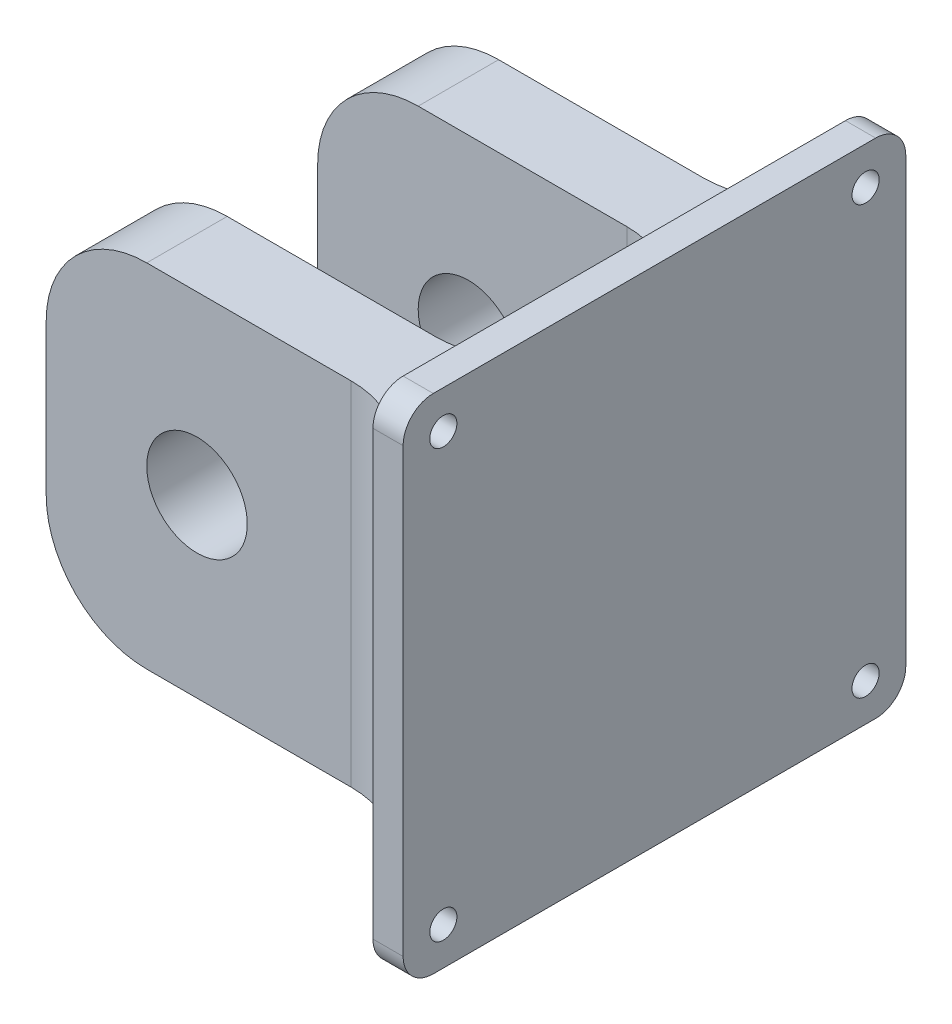
SolidWorks part; units mm, degrees
ref_plane "Plan de face" through (0, 0, 0) normal (0, 0, 1) x (1, 0, 0)
ref_plane "Plan de dessus" through (0, 0, 0) normal (0, 1, 0) x (1, 0, 0)
ref_plane "Plan de droite" through (0, 0, 0) normal (1, 0, 0) x (0, 0, -1)
sketch "Esquisse3" plane through (0, 0, 0) normal (1, 0, 0) x (0, 0, -1)
  line L1 (-25, -25) -> (25, -25)
  line L2 (-25, -25) -> (-25, 25)
  line L3 (-25, 25) -> (25, 25)
  line L4 (25, -25) -> (25, 25)
  line L5 (-25, -25) -> (25, 25) construction
  line L6 (-25, 25) -> (25, -25) construction
  point P0 (0, 0)
  dimension "D1" = 50
  dimension "D2" = 50
sketch "Esquisse4" plane through (0, 0, 0) normal (1, 0, 0) x (0, 0, -1)
  line L1 (-17.5, -17.5) -> (17.5, -17.5)
  line L2 (-17.5, -17.5) -> (-17.5, 17.5)
  line L3 (-17.5, 17.5) -> (17.5, 17.5)
  line L4 (17.5, -17.5) -> (17.5, 17.5)
  line L5 (-17.5, -17.5) -> (17.5, 17.5) construction
  line L6 (-17.5, 17.5) -> (17.5, -17.5) construction
  line L7 (17.5, -17.5) -> (9.5, -17.5)
  line L8 (17.5, -17.5) -> (17.5, 17.5)
  line L9 (17.5, 17.5) -> (9.5, 17.5)
  line L10 (9.5, -17.5) -> (9.5, 17.5)
  line L11 (-9.5, 17.5) -> (-17.5, 17.5)
  line L12 (-9.5, 17.5) -> (-9.5, -17.5)
  line L13 (-9.5, -17.5) -> (-17.5, -17.5)
  line L14 (-17.5, 17.5) -> (-17.5, -17.5)
  point P0 (0, 0)
  point P9 (0, 0)
  dimension "D1" = 35
  dimension "D2" = 35
  dimension "D3" = 8
  dimension "D4" = 8
extrude "Boss.-Extru.3" add sketch "Esquisse3" along normal blind 3
extrude "Boss.-Extru.5" add sketch "Esquisse4" against normal blind 40 contours L11 L2 L13 L12 | L7 L10 L9 L4
sketch "Esquisse7" plane through (0, 0, -17.5) normal (0, 0, -1) x (-1, 0, 0)
  line L0 (0, -17.5) -> (0, 17.5) construction
  circle A0 centre (25, 0) radius 5
  dimension "D1" = 25
extrude "Enlèv. mat.-Extru.1" cut sketch "Esquisse7" against normal blind 40 contours A0
fillet "Congé1" radius 10 6 edges at (0, 0, -17.5) (0, 0, 17.5) (-40, 17.5, 13.5) (-40, -17.5, 13.5) (-40, -17.5, -13.5) (-40, 17.5, -13.5)
fillet "Congé2" radius 9.25 2 edges at (0, 0, -9.5) (0, 0, 9.5)
fillet "Congé3" radius 3 4 edges at (1.5, -25, 25) (1.5, 25, 25) (1.5, 25, -25) (1.5, -25, -25)
sketch "Esquisse8" plane through (0, 0, 0) normal (-1, 0, 0) x (0, 0, 1)
  line L1 (-21, 21.25) -> (21, 21.25)
  line L2 (-21, 21.25) -> (-21, -21.25)
  line L3 (-21, -21.25) -> (21, -21.25)
  line L4 (21, 21.25) -> (21, -21.25)
  line L5 (-21, 21.25) -> (21, -21.25) construction
  line L6 (-21, -21.25) -> (21, 21.25) construction
  point P0 (0, 0)
  dimension "D1" = 42.5
  dimension "D2" = 42
hole_wizard "Dégagement M2.51" positions "Esquisse11" profile "Esquisse12" hole size "M2.5" standard "AS" end condition up to next
sketch "Esquisse11" plane through (0, 0, 0) normal (-1, 0, 0) x (0, 0, 1)
  point P0 (21, 21.25)
  point P3 (-21, 21.25)
  point P6 (-21, -21.25)
  point P9 (21, -21.25)
sketch "Esquisse12" plane through (0, 21.25, 21) normal (0, 1, 0) x (0, 0, 1)
  line L0 (0, 0) -> (0, 3)
  line L1 (0, 3) -> (1.35, 3)
  line L2 (1.35, 3) -> (1.35, 0)
  line L5 (1.35, 0) -> (0, 0)
  line L11 (0, -6.35) -> (0, 107.95) construction
  dimension "Diamètre du perçage jusqu'au prochain" = 2.7
  dimension "Profondeur du perçage jusqu'au prochain" = 3
